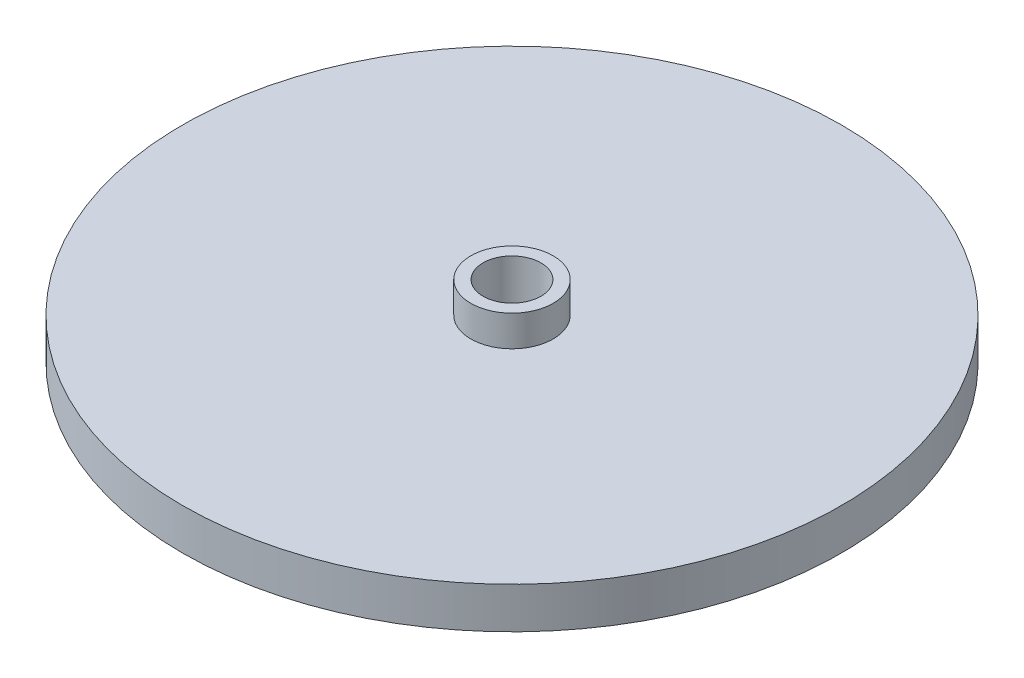
SolidWorks part; units mm, degrees
ref_plane "Front Plane" through (0, 0, 0) normal (0, 0, 1) x (1, 0, 0)
ref_plane "Top Plane" through (0, 0, 0) normal (0, 1, 0) x (1, 0, 0)
ref_plane "Right Plane" through (0, 0, 0) normal (1, 0, 0) x (0, 0, -1)
sketch "Sketch1" plane through (0, 0, 0) normal (0, 0, 1) x (1, 0, 0)
  line L1 (-101.6, 0) -> (-101.6, -12.7)
  line L2 (-101.6, -12.7) -> (-48.8213, -12.7)
  line L3 (-44.45, -12.7) -> (-44.45, -6.35)
  line L4 (-44.45, -6.35) -> (0, -6.35)
  line L5 (0, -6.35) -> (0, 0)
  line L6 (-101.6, 0) -> (0, 0)
  line L7 (-46.2813, -12.7) -> (-46.2813, -10.922)
  line L8 (-46.2813, -10.922) -> (-48.8213, -10.922)
  line L9 (-48.8213, -10.922) -> (-48.8213, -12.7)
  line L10 (-46.2813, -12.7) -> (-44.45, -12.7)
  point P8 (-50.8, -12.7)
  dimension "D1" = 101.6
  dimension "D2" = 12.7
  dimension "D3" = 6.35
  dimension "D4" = 44.45
  dimension "D5" = 50.8
  dimension "D6" = 2.54
  dimension "D7" = 1.778
  dimension "D8" = 46.2813
revolve "Revolve1" add sketch "Sketch1" angle 360 about L5
ref_plane "Plane1" through (0, 0, 0) normal (0, 1, 0) x (1, 0, 0)
sketch "Sketch2" plane through (0, 0, 0) normal (0, 1, 0) x (1, 0, 0)
  circle A0 centre (0, 0) radius 12.7
  dimension "D1" = 25.4
extrude "Boss-Extrude1" add sketch "Sketch2" along normal blind 9.525
ref_plane "Plane2" through (0, 9.525, 0) normal (0, 1, 0) x (1, 0, 0)
hole_wizard "Pipe Tap Drill for 1/2 Tap1" positions "Sketch4" profile "Sketch5" hole size "1/2" standard "ANSI Inch"
sketch "Sketch4" plane through (0, 9.525, 0) normal (0, 1, 0) x (1, 0, 0)
  point P0 (0, 0)
sketch "Sketch5" plane through (0, 9.525, 0) normal (1, 0, 0) x (0, 0, 1)
  line L0 (0, 0) -> (0, 37.1145)
  line L1 (0, 37.1145) -> (8.9281, 31.75)
  line L2 (8.9281, 31.75) -> (8.9281, 0)
  line L5 (8.9281, 0) -> (0, 0)
  line L10 (0, 37.1145) -> (-8.9281, 31.75) construction
  line L11 (0, -6.35) -> (0, 107.95) construction
  dimension "Hole Dia." = 17.8562
  dimension "Hole Depth" = 31.75
  dimension "Drill Angle" = 118
